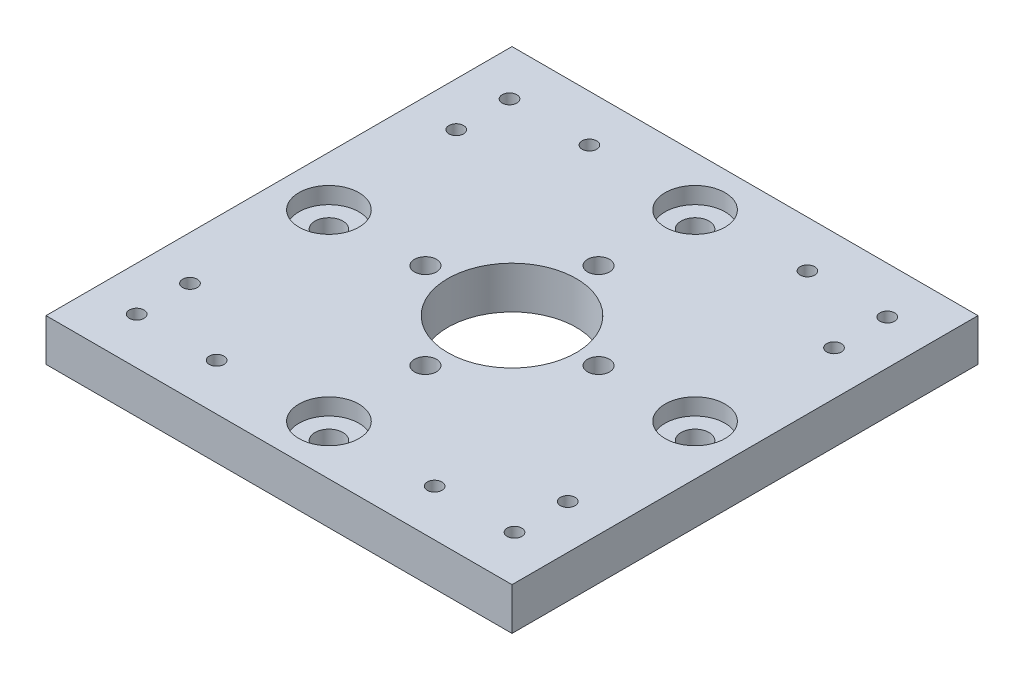
SolidWorks part; units mm, degrees
ref_plane "Front Plane" through (0, 0, 0) normal (0, 0, 1) x (1, 0, 0)
ref_plane "Top Plane" through (0, 0, 0) normal (0, 1, 0) x (1, 0, 0)
ref_plane "Right Plane" through (0, 0, 0) normal (1, 0, 0) x (0, 0, -1)
sketch "Sketch1" plane through (0, 0, 0) normal (0, 1, 0) x (1, 0, 0)
  line L1 (-35, -35) -> (35, -35)
  line L2 (-35, -35) -> (-35, 35)
  line L3 (-35, 35) -> (35, 35)
  line L4 (35, -35) -> (35, 35)
  line L5 (-35, -35) -> (35, 35) construction
  line L6 (-35, 35) -> (35, -35) construction
  circle A1 centre (0, 0) radius 13
  circle A2 centre (0, 13) radius 1.65
  circle A3 centre (13, 0) radius 1.65
  circle A4 centre (0, -13) radius 1.65
  circle A5 centre (-13, 0) radius 1.65
  point P1 (0, 0)
  dimension "D1" = 26
  dimension "D2" = 3.3
  dimension "D3" = 70
  dimension "D4" = 70
extrude "Boss-Extrude1" add sketch "Sketch1" along normal blind 6.35 contours A5 A1 A2 A3 A4 | A5 A1 A4 A3 A2 region at (-34.0101, 0, 0) region at (0, 0, 0)
sketch "Sketch2" plane through (0, 6.35, 0) normal (0, 1, 0) x (1, 0, 0)
  line L0 (0, 0) -> (0, 50000) construction
  line L1 (0, 0) -> (-50000, 0) construction
  circle A0 centre (16.375, 28) radius 1.1
  circle A1 centre (28.375, 28) radius 1.1
  circle A2 centre (28.375, 20) radius 1.1
  circle A3 centre (-28.375, 20) radius 1.1
  circle A4 centre (-28.375, 28) radius 1.1
  circle A5 centre (-16.375, 28) radius 1.1
  circle A6 centre (28.375, -20) radius 1.1
  circle A7 centre (28.375, -28) radius 1.1
  circle A8 centre (16.375, -28) radius 1.1
  circle A9 centre (-16.375, -28) radius 1.1
  circle A10 centre (-28.375, -20) radius 1.1
  circle A11 centre (-28.375, -28) radius 1.1
  dimension "D1" = 2.2
  dimension "D2" = 8
  dimension "D3" = 12
  dimension "D5" = 16.375
  dimension "D4" = 20
extrude "Cut-Extrude1" cut sketch "Sketch2" against normal up to next
sketch "Sketch3" plane through (0, 6.35, 0) normal (0, 1, 0) x (1, 0, 0)
  circle A0 centre (0, 0) radius 9.65
  dimension "D1" = 19.3
extrude "Cut-Extrude2" cut sketch "Sketch3" against normal up to next
sketch "Sketch4" plane through (0, 6.35, 0) normal (0, 1, 0) x (1, 0, 0)
  circle A0 centre (0, 0) radius 27.5
  circle A1 centre (0, 27.5) radius 2.1
  circle A2 centre (27.5, 0) radius 2.1
  circle A3 centre (0, -27.5) radius 2.1
  circle A4 centre (-27.5, 0) radius 2.1
  point P13 (0, 0)
  dimension "D1" = 55
  dimension "D2" = 4.2
  dimension "D3" = 4
extrude "Cut-Extrude3" cut sketch "Sketch4" against normal up to next contours A0 A4 | A0 A4 | A0 A1 | A0 A1 | A0 A2 | A0 A2 | A0 A3 | A0 A3 region at (26.5944, 6.35, 0) region at (28.3767, 6.35, 0) region at (0, 6.35, -26.5944) region at (0, 6.35, -28.3767) region at (0, 6.35, 28.3767) region at (0, 6.35, 26.5944) region at (-26.5944, 6.35, 0) region at (-28.3767, 6.35, 0)
sketch "Sketch5" plane through (0, 6.35, 0) normal (0, 1, 0) x (1, 0, 0)
  circle A0 centre (0, 27.5) radius 4.5
  circle A1 centre (27.5, 0) radius 4.5
  circle A2 centre (0, -27.5) radius 4.5
  circle A3 centre (-27.5, 0) radius 4.5
  dimension "D1" = 9
extrude "Cut-Extrude4" cut sketch "Sketch5" against normal blind 2.5
